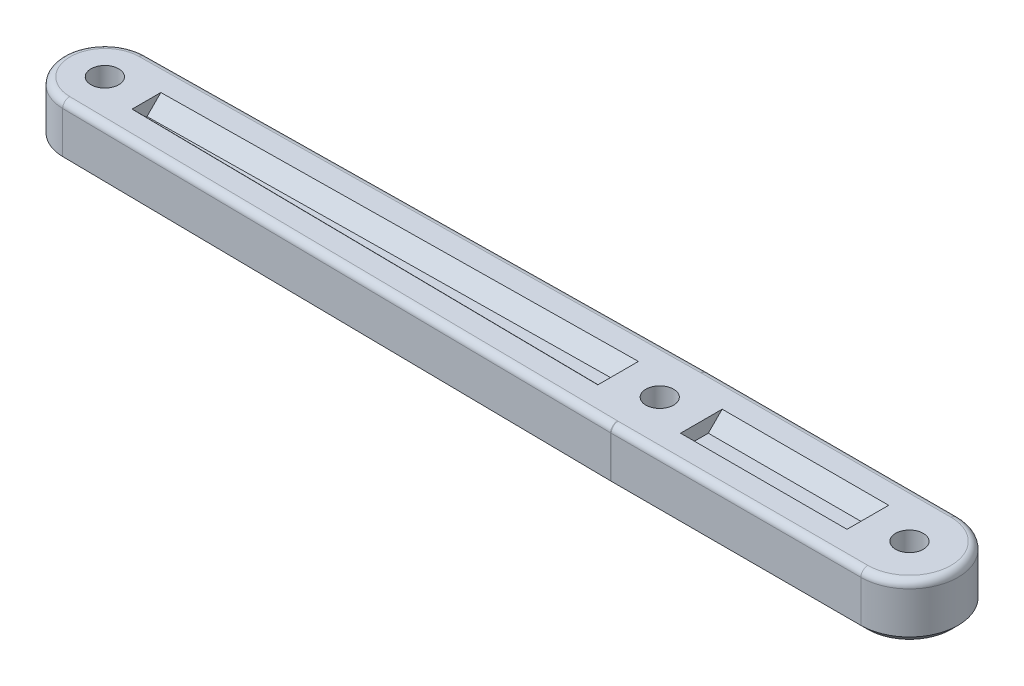
SolidWorks part; units mm, degrees
ref_plane "Front Plane" through (0, 0, 0) normal (0, 0, 1) x (1, 0, 0)
ref_plane "Top Plane" through (0, 0, 0) normal (0, 1, 0) x (1, 0, 0)
ref_plane "Right Plane" through (0, 0, 0) normal (1, 0, 0) x (0, 0, -1)
sketch "Sketch1" plane through (0, 0, 0) normal (0, 1, 0) x (1, 0, 0)
  line L0 (0, 7) -> (36, 7)
  line L1 (0, -7) -> (36, -7)
  line L2 (-80.075, 5.9995) -> (-0.0875, 6.9995)
  line L3 (-80.075, -5.9995) -> (-0.0875, -6.9995)
  circle A0 centre (0, 0) radius 2
  circle A1 centre (-80, 0) radius 2
  circle A2 centre (36, 0) radius 2
  arc A3 (-0.0875, -6.9995) -> (0, -7) centre (0, 0) ccw
  arc A4 (36, -7) -> (36, 7) centre (36, 0) ccw
  arc A5 (-80.075, 5.9995) -> (-80.075, -5.9995) centre (-80, 0) ccw
  arc A6 (0, 7) -> (-0.0875, 6.9995) centre (0, 0) ccw
  point P17 (-93.8057, 12.5897)
  point P18 (0, 0)
  point P19 (-89.1899, 35.4491)
  dimension "D1" = 4
  dimension "D2" = 4
  dimension "D3" = 4
  dimension "D6" = 14
  dimension "D7" = 14
  dimension "D8" = 12
  dimension "D4" = 80
  dimension "D5" = 36
extrude "Boss-Extrude1" add sketch "Sketch1" along normal blind 8
sketch "Sketch2" plane through (0, 8, 0) normal (0, 1, 0) x (1, 0, 0)
  line L0 (-74, 2.0752) -> (-6, 2.9252)
  line L1 (-6, 2.9252) -> (-6, -2.9252)
  line L2 (-6, -2.9252) -> (-74, -2.0752)
  line L3 (-74, -2.0752) -> (-74, 2.0752)
  line L4 (-0.0875, 6.9995) -> (-80.075, 5.9995) construction
  line L5 (-80.075, -5.9995) -> (-0.0875, -6.9995) construction
  line L6 (36, 7) -> (0, 7) construction
  line L7 (6, 3) -> (30, 3)
  line L8 (6, 3) -> (6, -3)
  line L9 (6, -3) -> (30, -3)
  line L10 (30, 3) -> (30, -3)
  line L11 (0, -7) -> (36, -7) construction
  circle A0 centre (-80, 0) radius 2 construction
  circle A1 centre (0, 0) radius 2 construction
  circle A2 centre (36, 0) radius 2 construction
  dimension "D1" = 4
  dimension "D2" = 4
  dimension "D3" = 6
  dimension "D4" = 6
  dimension "D5" = 4
  dimension "D6" = 4
  dimension "D7" = 6
  dimension "D8" = 6
extrude "Cut-Extrude1" cut sketch "Sketch2" against normal blind 2
sketch "Sketch3" plane through (0, 0, 0) normal (0, -1, 0) x (1, 0, 0)
  line L0 (-74, 2.0752) -> (-6, 2.9252) construction
  line L1 (-74, 2.0752) -> (-6, 2.9252)
  line L2 (-6, -2.9252) -> (-74, -2.0752) construction
  line L3 (-6, -2.9252) -> (-74, -2.0752)
  line L12 (-74, -2.0752) -> (-74, 2.0752) construction
  line L13 (-74, -2.0752) -> (-74, 2.0752)
  line L14 (-6, 2.9252) -> (-6, -2.9252) construction
  line L15 (-6, 2.9252) -> (-6, -2.9252)
  line L16 (6, -3) -> (6, 3) construction
  line L17 (6, -3) -> (6, 3)
  line L18 (30, -3) -> (6, -3) construction
  line L19 (30, -3) -> (6, -3)
  line L20 (6, 3) -> (30, 3) construction
  line L21 (6, 3) -> (30, 3)
  line L22 (30, 3) -> (30, -3) construction
  line L23 (30, 3) -> (30, -3)
extrude "Cut-Extrude2" cut sketch "Sketch3" against normal blind 2
fillet "Fillet2" radius 1 8 edges at (-0.0438, 8, 6.9999) (-40.0813, 8, 6.4995) (-86, 8, 0) (-40.0813, 8, -6.4995) (-0.0438, 8, -6.9999) (18, 8, -7) (43, 8, 0) (18, 8, 7)
chamfer "Chamfer1" distance 1 angle 45 8 edges at (18, 0, -7) (-0.0438, 0, -6.9999) (43, 0, 0) (-40.0813, 0, -6.4995) (18, 0, 7) (-86, 0, 0) (-0.0438, 0, 6.9999) (-40.0813, 0, 6.4995)
chamfer "Chamfer2" distance 2 angle 45 1 edges at (18, 2, -3)
chamfer "Chamfer3" distance 2 angle 45 1 edges at (18, 2, 3)
chamfer "Chamfer5" distance 2 angle 45 1 edges at (-40, 2, -2.5002)
chamfer "Chamfer6" distance 2 angle 45 1 edges at (-40, 2, 2.5002)
chamfer "Chamfer7" distance 2 angle 45 1 edges at (-40, 6, -2.5002)
chamfer "Chamfer8" distance 2 angle 45 1 edges at (18, 6, -3)
chamfer "Chamfer9" distance 2 angle 45 1 edges at (18, 6, 3)
chamfer "Chamfer10" distance 2 angle 45 1 edges at (-40, 6, 2.5002)
